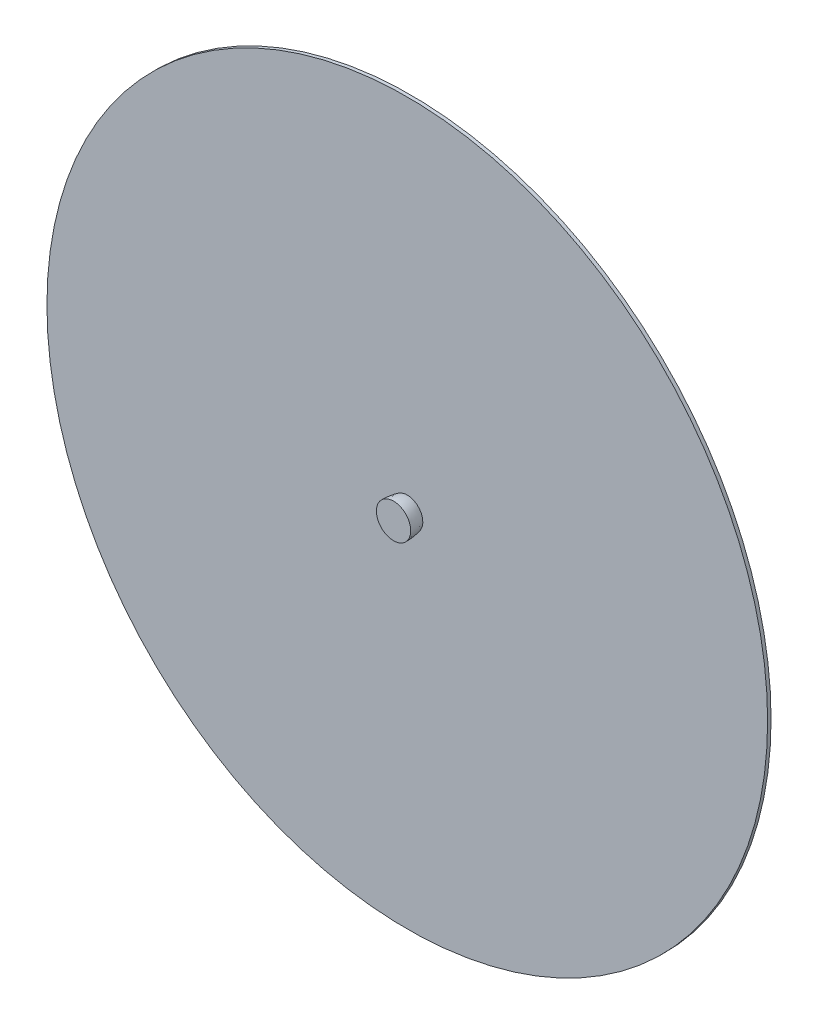
SolidWorks part; units mm, degrees
ref_plane "Plano frontal" through (0, 0, 0) normal (0, 0, 1) x (1, 0, 0)
ref_plane "Plano superior" through (0, 0, 0) normal (0, 1, 0) x (1, 0, 0)
ref_plane "Plano direito" through (0, 0, 0) normal (1, 0, 0) x (0, 0, -1)
sketch "Esboço1" plane through (0, 0, 0) normal (0, 1, 0) x (1, 0, 0)
  line L0 (0, 124.4382) -> (0, -114.8876) construction
  line L1 (0, 50) -> (0, -50)
  line L2 (0, -50) -> (-50, -50)
  line L3 (-50, -73.9133) -> (-50, 5.3002) construction
  line L4 (-50, -16.7821) -> (-50, -83.2179) construction
  spline S0 degree 3 poles (-50, -50) (-50, -12.7449) (-39.7951, 37.3746) (0, 50) knots 0 0 0 0 1 1 1 1
  point P11 (-36.8042, 16.236)
  point P12 (0, 0)
  dimension "D1" = 50
  dimension "D2" = 100
revolve "Revolução1" add sketch "Esboço1" angle 360 about L0
sketch "Esboço3" plane through (0, 0, 0) normal (0, 0, 1) x (1, 0, 0)
  circle A0 centre (0, 0) radius 1050
  dimension "D1" = 2100
extrude "Ressalto-extrusão2" add sketch "Esboço3" along normal blind 10 separate body
